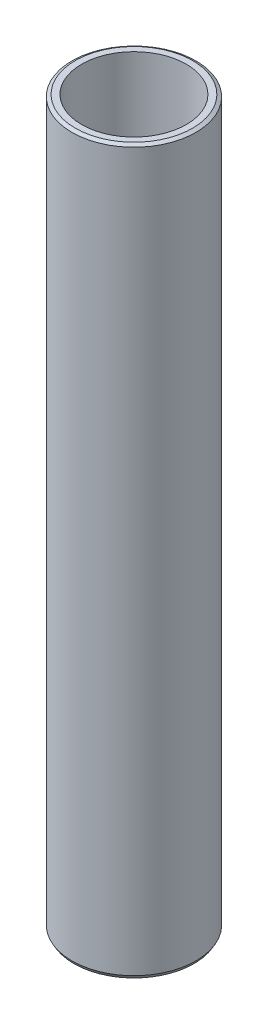
SolidWorks part; units mm, degrees
ref_plane "Front Plane" through (0, 0, 0) normal (0, 0, 1) x (1, 0, 0)
ref_plane "Top Plane" through (0, 0, 0) normal (0, 1, 0) x (1, 0, 0)
ref_plane "Right Plane" through (0, 0, 0) normal (1, 0, 0) x (0, 0, -1)
sketch "Sketch1" plane through (0, 0, 0) normal (0, 1, 0) x (1, 0, 0)
  circle A0 centre (0, 0) radius 40
  dimension "SHAFT_OD" = 80
extrude "Boss-Extrude1" add sketch "Sketch1" along normal blind 466.2599
sketch "Sketch2" plane through (0, 0, 0) normal (0, 1, 0) x (1, 0, 0)
  circle A0 centre (0, 0) radius 33.7627
  dimension "BORE_D" = 67.5254
extrude "Cut-Extrude1" cut sketch "Sketch2" along normal through all
chamfer "Chamfer1" distance 1.2572 angle 60 2 edges at (0, 466.2599, 40) (0, 0, 40) first distance on face at (0, 466.2599, 40) first distance on face at (0, 0, 33.7627)
